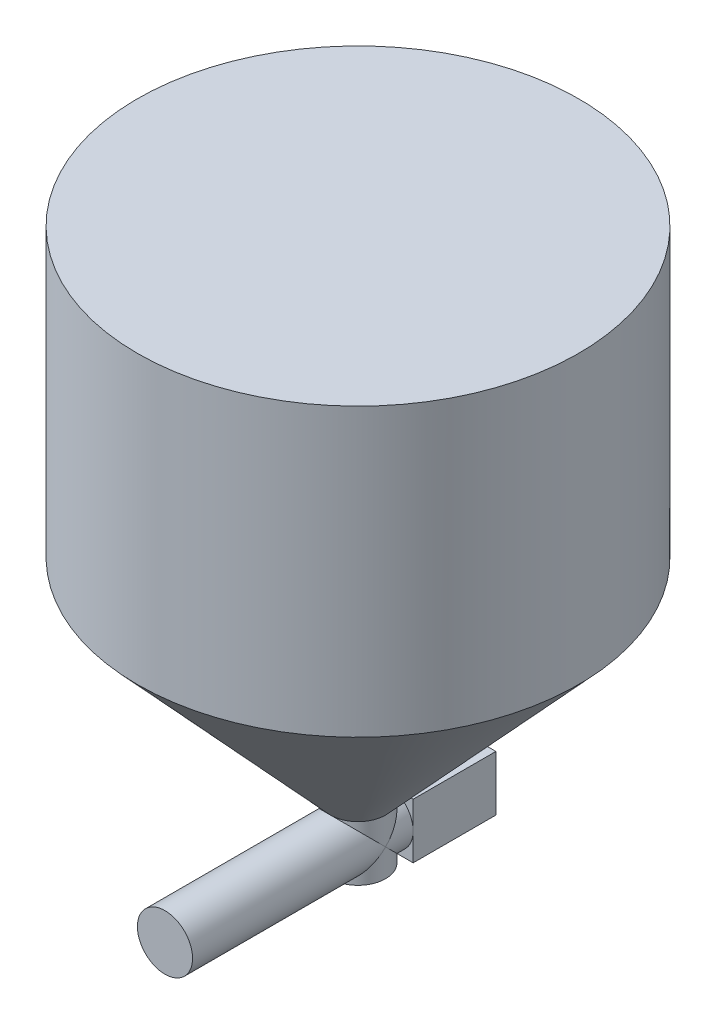
SolidWorks part; units mm, degrees
ref_plane "Alzado" through (0, 0, 0) normal (0, 0, 1) x (1, 0, 0)
ref_plane "Planta" through (0, 0, 0) normal (0, 1, 0) x (1, 0, 0)
ref_plane "Vista lateral" through (0, 0, 0) normal (1, 0, 0) x (0, 0, -1)
sketch "Croquis1" plane through (0, 0, 0) normal (0, 1, 0) x (1, 0, 0)
  circle A0 centre (0, 0) radius 400
  dimension "D1" = 800
ref_plane "Plano1" through (0, -900, 0) normal (0, 1, 0) x (1, 0, 0)
extrude "Saliente-Extruir1" add sketch "Croquis1" against normal blind 520 contours A0
sketch "Croquis2" plane through (0, -520, 0) normal (0, -1, 0) x (1, 0, 0)
  circle A0 centre (0, 0) radius 400
  dimension "D1" = 800
sketch "Croquis3" plane through (0, -900, 0) normal (0, 1, 0) x (1, 0, 0)
  circle A0 centre (0, 0) radius 50
  dimension "D1" = 100
loft "Recubrir1" add profiles "Croquis3", "Croquis2" connector at (-49.9253, -900, 2.7318) connector at (-399.2107, -520, 25.1162)
sketch "Croquis4" plane through (0, -900, 0) normal (0, -1, 0) x (1, 0, 0)
  circle A0 centre (0, 0) radius 50
extrude "Saliente-Extruir2" add sketch "Croquis4" along normal blind 100
ref_plane "Plano2" through (0, 0, -50) normal (0, 0, -1) x (-1, 0, 0)
sketch "Croquis5" plane through (0, 0, -50) normal (0, 0, -1) x (-1, 0, 0)
  line L0 (-50, -1000) -> (50, -1000) construction
  line L3 (0, -1000) -> (0, -900) construction
  line L4 (440, -900) -> (-440, -900) construction
  circle A0 centre (0, -950) radius 50
extrude "Saliente-Extruir3" add sketch "Croquis5" against normal blind 400
sketch "Croquis6" plane through (0, 0, -50) normal (0, 0, -1) x (-1, 0, 0)
  line L0 (50, -950) -> (-50, -950) construction
  line L2 (-50, -900) -> (50, -900)
  line L3 (-50, -900) -> (-50, -1000)
  line L4 (-50, -1000) -> (50, -1000)
  line L5 (50, -900) -> (50, -1000)
  line L6 (-50, -900) -> (50, -1000) construction
  line L7 (-50, -1000) -> (50, -900) construction
  circle A0 centre (0, -950) radius 50 construction
  circle A1 centre (0, -950) radius 50 construction
  point P4 (0, -950)
  point P8 (0, -950)
  dimension "D1" = 100
  dimension "D2" = 100
  dimension "D3" = 50
extrude "Saliente-Extruir4" add sketch "Croquis6" along normal blind 150
